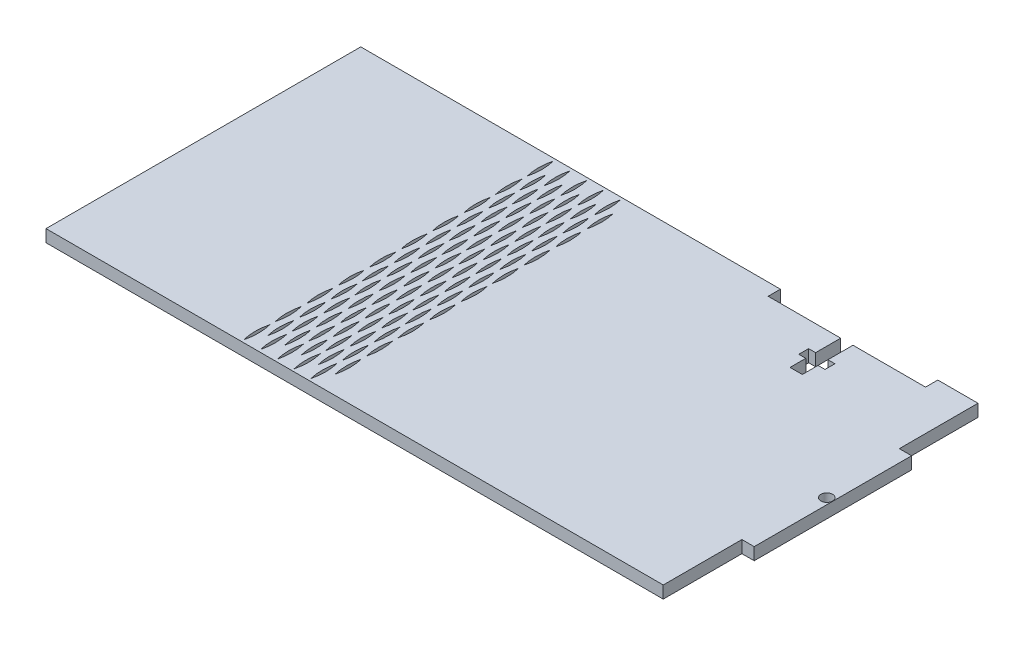
SolidWorks part; units mm, degrees
note: The reader was unsure of these and kept them because the rebuilt part matched: shared geometry of "Sketch5<3>".
ref_plane "Front Plane" through (0, 0, 0) normal (0, 0, 1) x (1, 0, 0)
ref_plane "Top Plane" through (0, 0, 0) normal (0, 1, 0) x (1, 0, 0)
ref_plane "Right Plane" through (0, 0, 0) normal (1, 0, 0) x (0, 0, -1)
sketch "Sketch1" plane through (0, 0, 0) normal (0, 1, 0) x (1, 0, 0)
  line L1 (-76.2, -38.1) -> (76.2, -38.1)
  line L2 (-76.2, -38.1) -> (-76.2, 38.1)
  line L3 (-76.2, 38.1) -> (76.2, 38.1)
  line L4 (76.2, -38.1) -> (76.2, 38.1)
  line L5 (-76.2, -38.1) -> (76.2, 38.1) construction
  line L6 (-76.2, 38.1) -> (76.2, -38.1) construction
  point P0 (0, 0)
  dimension "D1" = 152.4
  dimension "D2" = 76.2
extrude "Boss-Extrude1" add sketch "Sketch1" along normal blind 2.9718
sketch "Sketch2" plane through (0, 2.9718, 0) normal (0, 1, 0) x (1, 0, 0)
  line L0 (-76.2, 0) -> (76.2, 0) construction
  line L1 (-76.2, 38.1) -> (-76.2, -38.1) construction
  line L2 (76.2, -38.1) -> (76.2, 38.1) construction
  line L8 (76.2, 38.1) -> (73.2282, 38.1)
  line L9 (76.2, 38.1) -> (76.2, 19.05)
  line L10 (76.2, 19.05) -> (73.2282, 19.05)
  line L11 (73.2282, 38.1) -> (73.2282, 19.05)
  dimension "D1" = 19.05
  dimension "D2" = 2.9718
extrude "Cut-Extrude1" cut sketch "Sketch2" against normal through all
mirror "Mirror1" about plane through (0, 0, 0) normal (0, 0, 1) of "Cut-Extrude1"
sketch "Sketch4" plane through (0, 2.9718, 0) normal (0, 1, 0) x (1, 0, 0)
  line L0 (76.2, -19.05) -> (76.2, 19.05) construction
  circle A0 centre (74.7141, 0) radius 1.4224
  dimension "D2" = 2.8448
  dimension "D1" = 1.4859
extrude "Cut-Extrude3" cut sketch "Sketch4" against normal through all
sketch "Sketch5" plane through (0, 2.9718, 0) normal (0, 1, 0) x (1, 0, 0)
  line L0 (-12.7, 31.115) -> (-12.7, 37.465) construction
  line L2 (-76.2, 38.1) -> (-76.2, -38.1) construction
  line L3 (-10.668, 27.305) -> (-10.668, 33.655) construction
  line L4 (73.2282, 38.1) -> (-76.2, 38.1) construction
  arc A0 (-12.7, 31.115) -> (-12.7, 37.465) centre (-25.4, 34.29) ccw
  arc A1 (-12.7, 31.115) -> (-12.7, 37.465) centre (0, 34.29) cw
  arc A2 (-10.668, 27.305) -> (-10.668, 33.655) centre (-23.368, 30.48) ccw
  arc A3 (-10.668, 27.305) -> (-10.668, 33.655) centre (2.032, 30.48) cw
  point P5 (-12.7, 34.29)
  point P17 (-10.668, 30.48)
  dimension "D1" = 6.35
  dimension "D2" = 25.4
  dimension "D3" = 3.81
  dimension "D4" = 63.5
  dimension "D5" = 6.35
  dimension "D6" = 3.81
  dimension "D7" = 2.032
  dimension "D8" = 25.4
extrude "Cut-Extrude4" cut sketch "Sketch5" against normal through all contours A0 A1
pattern_linear "LPattern1" count 10 spacing 7.62 along (0, 0, 1) of "Cut-Extrude4"
extrude "Cut-Extrude6" cut sketch "Sketch5<3>" against normal through all
sketch "Sketch5<3>" plane through (0, 2.9718, 0) normal (0, 1, 0) x (1, 0, 0) same geometry as "Sketch5"
pattern_linear "LPattern2" count 9 spacing 7.62 along (0, 0, 1) of "Cut-Extrude6"
pattern_linear "LPattern3" count 5 spacing 4.064 along (-1, 0, 0) of "LPattern2", "LPattern1", "Cut-Extrude4", "Cut-Extrude6"
sketch "Sketch6" plane through (0, 2.9718, 0) normal (0, 1, 0) x (1, 0, 0)
  line L0 (73.2282, 38.1) -> (-76.2, 38.1) construction
  line L1 (-63.5, 38.1) -> (-25.4, 38.1)
  line L2 (-63.5, 38.1) -> (-63.5, 35.1282)
  line L3 (-63.5, 35.1282) -> (-25.4, 35.1282)
  line L4 (-25.4, 38.1) -> (-25.4, 35.1282)
  line L5 (76.2, -19.05) -> (76.2, 19.05) construction
  line L6 (25.4, 38.1) -> (63.5, 38.1)
  line L7 (25.4, 38.1) -> (25.4, 35.1282)
  line L8 (25.4, 35.1282) -> (63.5, 35.1282)
  line L9 (63.5, 38.1) -> (63.5, 35.1282)
  line L10 (-76.2, 38.1) -> (-76.2, -38.1) construction
  line L11 (-44.45, 35.1282) -> (-44.45, 38.1) construction
  line L12 (44.45, 35.1282) -> (44.45, 38.1) construction
  line L14 (-45.9359, 22.86) -> (-42.9641, 22.86)
  line L15 (-45.9359, 22.86) -> (-45.9359, 35.1282)
  line L16 (-45.9359, 35.1282) -> (-42.9641, 35.1282)
  line L17 (-42.9641, 22.86) -> (-42.9641, 35.1282)
  line L18 (-45.9359, 22.86) -> (-42.9641, 35.1282) construction
  line L19 (-45.9359, 35.1282) -> (-42.9641, 22.86) construction
  line L20 (42.9641, 22.86) -> (45.9359, 22.86)
  line L21 (42.9641, 22.86) -> (42.9641, 35.1282)
  line L22 (42.9641, 35.1282) -> (45.9359, 35.1282)
  line L23 (45.9359, 22.86) -> (45.9359, 35.1282)
  line L24 (42.9641, 22.86) -> (45.9359, 35.1282) construction
  line L25 (42.9641, 35.1282) -> (45.9359, 22.86) construction
  line L26 (42.9641, 29.0513) -> (41.275, 29.0513)
  line L27 (42.9641, 29.0513) -> (42.9641, 26.67)
  line L28 (42.9641, 26.67) -> (41.275, 26.67)
  line L29 (41.275, 29.0513) -> (41.275, 26.67)
  line L30 (45.9359, 29.0513) -> (47.625, 29.0513)
  line L31 (45.9359, 29.0513) -> (45.9359, 26.67)
  line L32 (45.9359, 26.67) -> (47.625, 26.67)
  line L33 (47.625, 29.0513) -> (47.625, 26.67)
  line L34 (-42.9641, 29.0513) -> (-41.275, 29.0513)
  line L35 (-42.9641, 29.0513) -> (-42.9641, 26.67)
  line L36 (-42.9641, 26.67) -> (-41.275, 26.67)
  line L37 (-41.275, 29.0513) -> (-41.275, 26.67)
  line L38 (-45.9359, 29.0513) -> (-47.625, 29.0513)
  line L39 (-45.9359, 29.0513) -> (-45.9359, 26.67)
  line L40 (-45.9359, 26.67) -> (-47.625, 26.67)
  line L41 (-47.625, 29.0513) -> (-47.625, 26.67)
  point P18 (-44.45, 28.9941)
  point P23 (44.45, 28.9941)
  dimension "D1" = 38.1
  dimension "D2" = 38.1
  dimension "D3" = 2.9718
  dimension "D4" = 2.9718
  dimension "D5" = 12.7
  dimension "D6" = 12.7
  dimension "D7" = 15.24
  dimension "D8" = 2.9718
  dimension "D9" = 2.9718
  dimension "D10" = 15.24
  dimension "D11" = 6.35
  dimension "D12" = 6.35
  dimension "D13" = 3.175
  dimension "D14" = 2.3813
  dimension "D15" = 3.175
  dimension "D16" = 3.81
extrude "Cut-Extrude7" cut sketch "Sketch6" against normal through all contours L9 L6 L7 L8 | L20 L23 L8 L21 | L33 L30 L23 L32 | L26 L29 L28 L21 | L34 L37 L36 L35 | L38 L41 L40 L39 | L15 L16 L17 L14 | L3 L4 L1 L2
